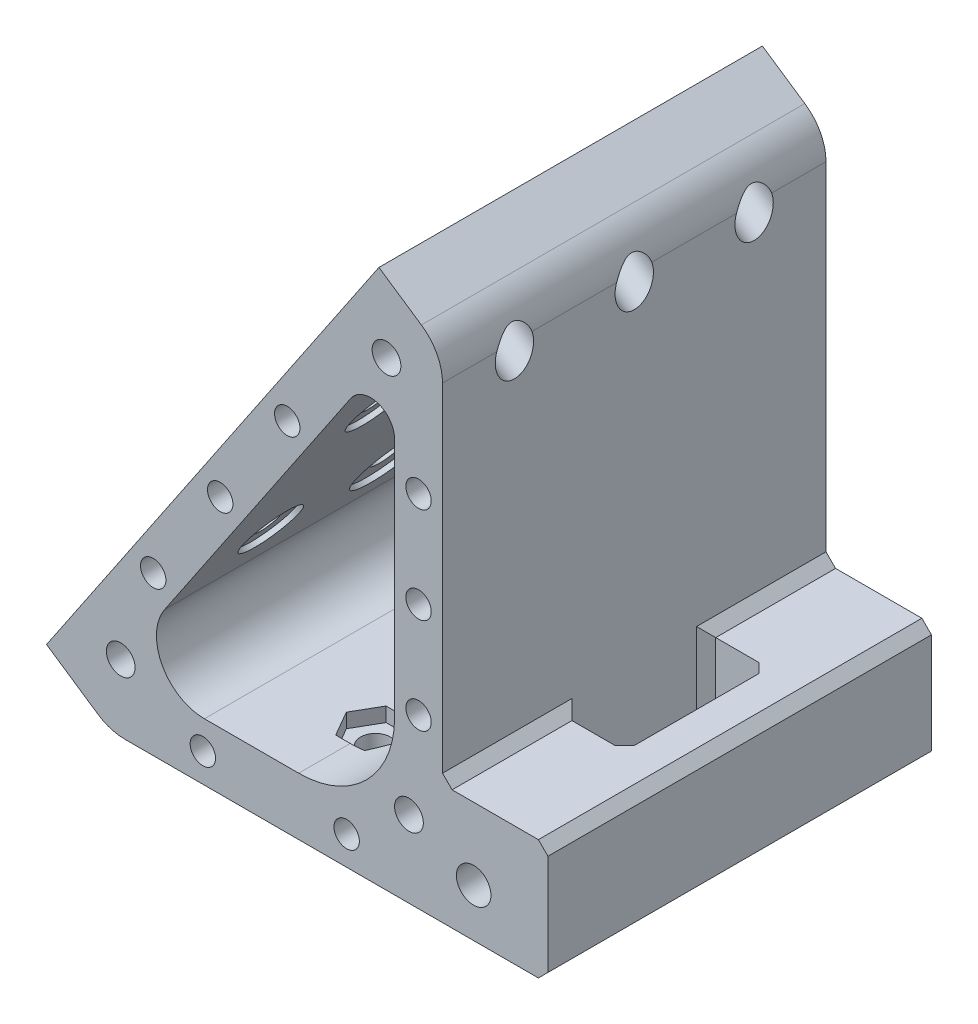
SolidWorks part; units mm, degrees
ref_plane "Спереди" through (0, 0, 0) normal (0, 0, 1) x (1, 0, 0)
ref_plane "Сверху" through (0, 0, 0) normal (0, 1, 0) x (1, 0, 0)
ref_plane "Справа" through (0, 0, 0) normal (1, 0, 0) x (0, 0, -1)
sketch "Эскиз1" plane through (0, 0, 0) normal (0, 0, 1) x (1, 0, 0)
  line L0 (0, 102.8007) -> (-69.3399, 0)
  line L1 (-69.3399, 0) -> (0, 0)
  line L2 (0, 0) -> (0, 102.8007)
  dimension "D1" = 56
  dimension "D2" = 124
extrude "Бобышка-Вытянуть1" add sketch "Эскиз1" along normal blind 80
sketch "Эскиз2" plane through (-47.6576, 32.1454, 0) normal (-0.829, 0.5592, 0) x (0, 0, 1)
  line L4 (0, 85.2256) -> (0, -38.7744)
  line L5 (0, -38.7744) -> (80, -38.7744)
  line L6 (80, -38.7744) -> (80, 85.2256)
  line L7 (80, 85.2256) -> (0, 85.2256)
  line L8 (0, 85.2256) -> (0, -38.7744)
  line L9 (0, -38.7744) -> (80, -38.7744)
  line L10 (80, -38.7744) -> (80, 85.2256)
  line L11 (80, 85.2256) -> (0, 85.2256)
  dimension "D1" = 0
extrude "Бобышка-Вытянуть2" add sketch "Эскиз2" along normal blind 16
fillet "Скругление1" radius 10 2 edges at (0, 102.8007, 40) (-69.3399, 0, 40)
sketch "Эскиз3" plane through (0, 0, 80) normal (0, 0, 1) x (1, 0, 0)
  line L1 (-19.1452, 85.1465) -> (-57.9662, 27.5919)
  line L3 (-10, 32) -> (-10, 82.3505)
  line L4 (-49.6759, 12) -> (-30, 12)
  line L5 (-82.6045, 8.9471) -> (-13.2646, 111.7477) construction
  line L6 (0, 0) -> (0, 97.4836) construction
  line L7 (-66.2826, 0) -> (0, 0) construction
  arc A6 (-10, 32) -> (-30, 12) centre (-30, 32) cw
  arc A7 (-49.6759, 12) -> (-57.9662, 27.5919) centre (-49.6759, 22) cw
  arc A8 (-10, 82.3505) -> (-19.1452, 85.1465) centre (-15, 82.3505) ccw
  dimension "D5" = 20
  dimension "D6" = 10
  dimension "D4" = 5
  dimension "D2" = 10
  dimension "D3" = 12
  dimension "D1" = 10
extrude "Вырез-Вытянуть1" cut sketch "Эскиз3" against normal up to surface (80 mm away) up to face at (-33.9327, 46.5419, 0)
sketch "Эскиз4" plane through (-60.9222, 41.0925, 0) normal (-0.829, 0.5592, 0) x (0, 0, 1)
  line L0 (0, 23.2256) -> (80, 23.2256) construction
  line L1 (0, 85.2256) -> (0, -38.7744) construction
  line L2 (80, -38.7744) -> (80, 85.2256) construction
  line L3 (80, 85.2256) -> (0, 85.2256) construction
  line L4 (40, 85.2256) -> (40, -38.7744) construction
  line L5 (0, -38.7744) -> (80, -38.7744) construction
  line L6 (15, 79.2256) -> (40, 79.2256) construction
  line L7 (40, 79.2256) -> (65, 79.2256) construction
  line L8 (65, 43.2256) -> (65, 85.2256) construction
  line L9 (65, 43.2256) -> (65, 23.2256) construction
  line L10 (15, 43.2256) -> (40, 43.2256) construction
  line L11 (40, 43.2256) -> (65, 43.2256) construction
  line L12 (40, 3.2256) -> (65, 3.2256) construction
  line L13 (15, 3.2256) -> (40, 3.2256) construction
  line L14 (65, 3.2256) -> (65, -38.7744) construction
  line L15 (40, -32.7744) -> (65, -32.7744) construction
  line L16 (15, -32.7744) -> (40, -32.7744) construction
  circle A0 centre (40, 79.2256) radius 2
  circle A1 centre (15, 79.2256) radius 2
  circle A2 centre (65, 79.2256) radius 2
  circle A3 centre (15, 43.2256) radius 2.5
  circle A4 centre (40, 43.2256) radius 3
  circle A5 centre (65, 43.2256) radius 2.5
  circle A9 centre (65, 3.2256) radius 2.5
  circle A10 centre (40, 3.2256) radius 3
  circle A11 centre (15, 3.2256) radius 2.5
  circle A12 centre (65, -32.7744) radius 2
  circle A13 centre (15, -32.7744) radius 2
  circle A14 centre (40, -32.7744) radius 2
  dimension "D1" = 4
  dimension "D2" = 5
  dimension "D7" = 6
  dimension "D3" = 6
  dimension "D4" = 25
  dimension "D5" = 25
  dimension "D6" = 20
extrude "Вырез-Вытянуть2" cut sketch "Эскиз4" against normal blind 20
ref_plane "Плоскость1" through (-31.9058, 21.5208, 0) normal (-0.829, 0.5592, 0) x (0, 0, 1)
ref_axis "Ось1" through (-13.2646, 111.7477, 40) along (-0.5592, -0.829, 0)
ref_plane "Плоскость2" through (0, 0, 40) normal (0, 0, -1) x (-0.5592, -0.829, 0)
sketch "Эскиз6" plane through (-31.9058, 21.5208, 0) normal (-0.829, 0.5592, 0) x (0, 0, 1)
  circle A0 centre (65, -32.7744) radius 4
  circle A1 centre (40, -32.7744) radius 4
  circle A2 centre (15, -32.7744) radius 4
  circle A3 centre (65, 79.2256) radius 4
  circle A4 centre (40, 79.2256) radius 4
  circle A5 centre (15, 79.2256) radius 4
  dimension "D1" = 8
extrude "Вырез-Вытянуть3" cut sketch "Эскиз6" along normal offset from surface (23 mm away) 12 up to face at (-78.131, 15.5794, 65)
sketch "Эскиз12" plane through (0, 0, 0) normal (0, 0, -1) x (-1, 0, 0)
  line L0 (66.2826, 0) -> (0, 0) construction
  line L1 (0, 0) -> (-22, 0)
  line L2 (0, 0) -> (0, 25)
  line L3 (0, 25) -> (-22, 25)
  line L4 (-22, 0) -> (-22, 25)
  line L5 (0, 0) -> (0, 97.4836) construction
  dimension "D1" = 22
  dimension "D2" = 25
sketch "Эскиз15" plane through (0, 0, 80) normal (0, 0, 1) x (1, 0, 0)
  line L0 (-46.3697, 53.7259) -> (-60.3495, 33) construction
  line L1 (-50, 6) -> (-20, 6) construction
  line L2 (-82.6045, 8.9471) -> (-13.2646, 111.7477) construction
  line L3 (0, 0) -> (0, 97.4836) construction
  line L4 (-66.2826, 0) -> (0, 0) construction
  line L6 (-5, 75) -> (-5, 55) construction
  line L7 (-5, 55) -> (-5, 35) construction
  line L9 (-13.2646, 111.7477) -> (-4.4081, 105.7739) construction
  line L11 (-46.3697, 53.7259) -> (-32.3899, 74.4519) construction
  circle A0 centre (-7, 16) radius 3
  circle A1 centre (-11.6845, 96.2074) radius 3
  circle A6 centre (-67.1341, 14) radius 3
  circle A7 centre (-60.3495, 33) radius 2.65
  circle A8 centre (-46.3697, 53.7259) radius 2.65
  circle A9 centre (-32.3899, 74.4519) radius 2.65
  circle A10 centre (-50, 6) radius 2.65
  circle A12 centre (-20, 6) radius 2.65
  circle A13 centre (-5, 75) radius 2.65
  circle A14 centre (-5, 55) radius 2.65
  circle A15 centre (-5, 35) radius 2.65
  dimension "D2" = 6
  dimension "D6" = 5.3
  dimension "D3" = 35
  dimension "D4" = 50
  dimension "D5" = 5
  dimension "D7" = 6
  dimension "D8" = 30
  dimension "D9" = 20
  dimension "D10" = 16
  dimension "D11" = 7
  dimension "D12" = 40
  dimension "D13" = 10
  dimension "D14" = 12
  dimension "D15" = 5
  dimension "D16" = 33
  dimension "D17" = 14
  dimension "D18" = 10
sketch "Эскиз17" plane through (-52.6318, 35.5006, 0) normal (0.829, -0.5592, 0) x (0, 0, -1)
  circle A0 centre (-65, 43.2256) radius 6
  circle A1 centre (-40, 43.2256) radius 7.5
  circle A2 centre (-15, 43.2256) radius 6
  circle A3 centre (-65, 3.2256) radius 6
  circle A4 centre (-40, 3.2256) radius 7.5
  circle A5 centre (-15, 3.2256) radius 6
  dimension "D1" = 12
  dimension "D2" = 15
extrude "Бобышка-Вытянуть3" add sketch "Эскиз12" against normal up to surface (80 mm away) up to face at (-29.3825, 41.3066, 80)
extrude "Вырез-Вытянуть12" cut sketch "Эскиз17" against normal blind 1 and the other way blind 1
extrude "Вырез-Вытянуть13" cut sketch "Эскиз15" against normal blind 8
mirror "Зеркальное отражение1" about plane through (0, 0, 40) normal (0, 0, -1) of "Вырез-Вытянуть13"
sketch "Эскиз18" plane through (0, 0, 0) normal (0, -1, 0) x (1, 0, 0)
  line L0 (-82.6045, 40) -> (22, 40) construction
  line L1 (-82.6045, 0) -> (-82.6045, 80) construction
  line L2 (22, 80) -> (22, 0) construction
  line L3 (0, 80) -> (0, 0) construction
  line L5 (0, 55) -> (13, 55)
  line L6 (0, 55) -> (0, 25)
  line L7 (0, 25) -> (13, 25)
  line L8 (13, 55) -> (13, 25)
  circle A0 centre (-30, 40) radius 30 construction
  point P14 (13, 40)
  dimension "D1" = 60
  dimension "D2" = 30
  dimension "D3" = 13
extrude "Вырез-Вытянуть14" cut sketch "Эскиз18" against normal up to surface (25 mm away) up to face at (11, 25, 40)
sketch "Эскиз19" plane through (0, 0, 0) normal (0, -1, 0) x (1, 0, 0)
  line L0 (-82.6045, 40) -> (22, 40) construction
  line L1 (-82.6045, 0) -> (-82.6045, 80) construction
  line L2 (22, 80) -> (22, 0) construction
  line L3 (0, 80) -> (0, 55) construction
  circle A0 centre (-30, 40) radius 30 construction
  circle A1 centre (-30, 40) radius 24 construction
  circle A2 centre (-30, 64) radius 3.1
  circle A3 centre (-9.2154, 52) radius 3.1
  circle A4 centre (-9.2154, 28) radius 3.1
  circle A5 centre (-30, 16) radius 3.1
  circle A6 centre (-50.7846, 28) radius 3.1
  circle A7 centre (-50.7846, 52) radius 3.1
  circle A8 centre (-30, 40) radius 7.5
  point P25 (-30, 40)
  dimension "D1" = 60
  dimension "D2" = 48
  dimension "D3" = 6.2
  dimension "D5" = 15
  dimension "D4" = 6
extrude "Вырез-Вытянуть15" cut sketch "Эскиз19" against normal blind 8
sketch "Эскиз20" plane through (0, 0, 80) normal (0, 0, 1) x (1, 0, 0)
  line L0 (0, 12.5) -> (13, 12.5) construction
  line L1 (0, 25) -> (0, 0) construction
  line L2 (13, 25) -> (13, 0) construction
  line L3 (-66.2826, 0) -> (22, 0) construction
  circle A0 centre (6.5, 10) radius 3.6
  point P11 (6.5, 12.5)
  dimension "D2" = 7.2
  dimension "D1" = 10
extrude "Вырез-Вытянуть16" cut sketch "Эскиз20" against normal up to surface (80 mm away) up to face at (-17.35, 6, 0)
chamfer "Фаска1" distance 2 angle 45 8 edges at (22, 0, 40) (22, 25, 40) (13, 12.5, 55) (0, 25, 67.5) (0, 12.5, 55) (13, 12.5, 25) (0, 25, 12.5) (0, 12.5, 25)
sketch "Эскиз21" plane through (0, 0, 80) normal (0, 0, 1) x (1, 0, 0)
  circle A0 centre (-11.6845, 96.2074) radius 3
  circle A1 centre (-67.1341, 14) radius 3
  circle A2 centre (-7, 16) radius 3
  circle A3 centre (-11.6845, 96.2074) radius 3 construction
extrude "Вырез-Вытянуть17" cut sketch "Эскиз21" against normal up to surface (80 mm away) up to face at (2.9, 10, 0)
sketch "Эскиз22" plane through (0, 12, 0) normal (0, 1, 0) x (1, 0, 0)
  line L1 (-26.9689, -10.75) -> (-33.0311, -10.75)
  line L2 (-33.0311, -10.75) -> (-36.0622, -16)
  line L3 (-36.0622, -16) -> (-33.0311, -21.25)
  line L4 (-33.0311, -21.25) -> (-26.9689, -21.25)
  line L5 (-26.9689, -21.25) -> (-23.9378, -16)
  line L6 (-23.9378, -16) -> (-26.9689, -10.75)
  line L7 (-33.0311, -58.75) -> (-36.0622, -64)
  line L8 (-36.0622, -64) -> (-33.0311, -69.25)
  line L9 (-33.0311, -69.25) -> (-26.9689, -69.25)
  line L10 (-26.9689, -69.25) -> (-23.9378, -64)
  line L11 (-23.9378, -64) -> (-26.9689, -58.75)
  line L12 (-26.9689, -58.75) -> (-33.0311, -58.75)
  circle A0 centre (-30, -16) radius 5.25 construction
  circle A1 centre (-30, -64) radius 5.25 construction
  dimension "D1" = 10.5
extrude "Вырез-Вытянуть18" cut sketch "Эскиз22" against normal blind 3 and the other way blind 10
sketch "Эскиз23" plane through (0, 0, 0) normal (0, -1, 0) x (1, 0, 0)
  circle A0 centre (-30, 64) radius 3.1
  circle A1 centre (-30, 64) radius 3.1 construction
  circle A2 centre (-30, 16) radius 3.1
  circle A3 centre (-30, 16) radius 3.1 construction
extrude "Вырез-Вытянуть19" cut sketch "Эскиз23" against normal up to surface (12 mm away) up to face at (-34.5429, 12, 40)
